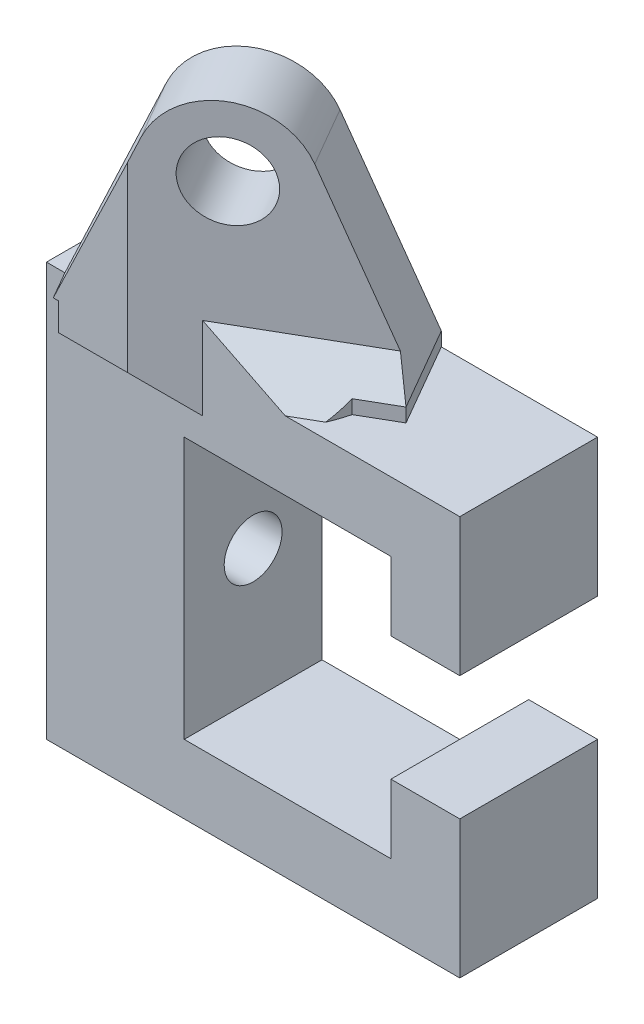
SolidWorks part; units mm, degrees
ref_plane "Front Plane" through (0, 0, 0) normal (0, 0, 1) x (1, 0, 0)
ref_plane "Top Plane" through (0, 0, 0) normal (0, 1, 0) x (1, 0, 0)
ref_plane "Right Plane" through (0, 0, 0) normal (1, 0, 0) x (0, 0, -1)
sketch "Sketch1" plane through (0, 0, 0) normal (0, 0, 1) x (1, 0, 0)
  line L0 (0, 0) -> (0, -23031.2068) construction
  line L1 (0, 0) -> (23031.2068, 0) construction
  line L2 (15, 5) -> (15, 0)
  line L3 (15, 0) -> (0, 0)
  line L4 (0, 0) -> (0, 19)
  line L5 (0, 19) -> (15, 19)
  line L6 (15, 19) -> (15, 14)
  line L7 (15, 14) -> (20, 14)
  line L8 (20, 14) -> (20, 24)
  line L9 (20, 24) -> (-10, 24)
  line L10 (-10, 24) -> (-10, -5)
  line L11 (-10, -5) -> (20, -5)
  line L12 (20, -5) -> (20, 5)
  line L13 (20, 5) -> (15, 5)
  dimension "D1" = 19
  dimension "D2" = 15
  dimension "D3" = 15
  dimension "D4" = 5
  dimension "D5" = 5
  dimension "D6" = 5
  dimension "D7" = 5
  dimension "D8" = 5
  dimension "D9" = 10
extrude "Boss-Extrude1" add sketch "Sketch1" along normal mid plane 10
sketch "Sketch2" plane through (-10, 0, 0) normal (-1, 0, 0) x (0, 0, 1)
  line L0 (0, 24) -> (0, -49976) construction
  line L1 (5, 24) -> (-5, 24) construction
  line L2 (-5, 9.5) -> (49995, 9.5) construction
  line L3 (-5, 24) -> (-5, -5) construction
  circle A0 centre (0, 9.5) radius 2.1
  point P4 (0, 24)
  point P9 (-5, 9.5)
  dimension "D1" = 4.2
extrude "Cut-Extrude1" cut sketch "Sketch2" against normal blind 10
sketch "Sketch3" plane through (0, 24, 0) normal (0, 1, 0) x (1, 0, 0)
  line L0 (0, -5) -> (0, 5) construction
  line L1 (0, -5) -> (0, 5) construction
  circle A0 centre (0, 0) radius 10
  dimension "D1" = 20
extrude "Boss-Extrude2" add sketch "Sketch3" along normal blind 1
ref_axis "Axis1" through (0, 30.7, 0) along (0, -1, 0)
ref_plane "Plane1" through (0, 0, 0) normal (0.5, 0, 0.866) x (0, -1, 0)
sketch "Sketch4" plane through (0, 0, 0) normal (0.5, 0, 0.866) x (0.866, 0, -0.5)
  line L0 (10, 25) -> (-10, 25) construction
  line L1 (10, 25) -> (-10, 25)
  line L2 (0, 29) -> (0, 50029) construction
  line L3 (-10, 25) -> (-4.6154, 37.9231)
  line L4 (10, 25) -> (4.6154, 37.9231)
  circle A0 centre (0, 36) radius 2.75
  circle A1 centre (0, 36) radius 10 construction
  arc A3 (4.6154, 37.9231) -> (-4.6154, 37.9231) centre (0, 36) ccw
  point P4 (0, 25)
  dimension "D1" = 5.5
  dimension "D2" = 20
  dimension "D3" = 11
  dimension "D4" = 10
extrude "Boss-Extrude3" add sketch "Sketch4" along normal blind 5
sketch "Sketch5" plane through (0, -5, 0) normal (0, -1, 0) x (1, 0, 0)
  line L0 (-20, -15) -> (30, -15)
  line L1 (30, -15) -> (30, 15)
  line L2 (30, 15) -> (-20, 15)
  line L3 (-20, 15) -> (-20, -15)
  line L4 (-10, -5) -> (20, -5)
  line L5 (20, -5) -> (20, 5)
  line L6 (20, 5) -> (-10, 5)
  line L7 (-10, 5) -> (-10, -5)
  line L8 (-10, -5) -> (20, -5)
  line L9 (20, -5) -> (20, 5)
  line L10 (20, 5) -> (-10, 5)
  line L11 (-10, 5) -> (-10, -5)
  line L12 (-12, -7) -> (22, -7)
  line L13 (22, -7) -> (22, 7)
  line L14 (22, 7) -> (-12, 7)
  line L15 (-12, 7) -> (-12, -7)
  dimension "D1" = 0
  dimension "D2" = 10
  dimension "D3" = 2
extrude "Cut-Extrude2" cut sketch "Sketch5" against normal through all contours L2 L3 L0 L1 L15 L14 L13 L12 region at (-19.4169, -5, 0)
sketch "Sketch6" plane through (0, 25, 0) normal (0, 1, 0) x (1, 0, 0)
  line L3 (7.1414, 7) -> (-7.1414, 7)
  line L4 (-8.6603, -5) -> (8.6603, 5)
  line L6 (7.1414, 7) -> (-7.1414, 7)
  line L7 (-8.6603, -5) -> (8.6603, 5)
  arc A1 (8.6603, 5) -> (7.1414, 7) centre (0, 0) ccw
  arc A4 (-7.1414, 7) -> (-8.6603, -5) centre (0, 0) ccw
  arc A5 (-7.1414, 7) -> (-8.6603, -5) centre (0, 0) ccw
  arc A6 (8.6603, 5) -> (7.1414, 7) centre (0, 0) ccw
  dimension "D1" = 0
extrude "Cut-Extrude3" cut sketch "Sketch6" against normal blind 1
sketch "Sketch7" plane through (0, 25, 0) normal (0, 1, 0) x (1, 0, 0)
  line L2 (-2.1244, -7) -> (7.1414, -7)
  line L3 (10, 0) -> (-2.1244, -7)
  line L4 (-2.1244, -7) -> (7.1414, -7)
  line L5 (10, 0) -> (-2.1244, -7)
  arc A1 (7.1414, -7) -> (10, 0) centre (0, 0) ccw
  arc A2 (7.1414, -7) -> (10, 0) centre (0, 0) ccw
  dimension "D1" = 0
extrude "Cut-Extrude4" cut sketch "Sketch7" against normal blind 1
chamfer "Chamfer1" distance 3 angle 45 1 edges at (5.6699, 24, 2.5)
chamfer "Chamfer2" distance 3 angle 45 1 edges at (-3.6603, 24, 5)
sketch "Sketch8" plane through (0, -5, 0) normal (0, -1, 0) x (1, 0, 0)
  line L0 (-10, 5) -> (-10, -5) construction
  line L1 (-10, -13.16) -> (-20.9807, -13.16)
  line L2 (-10, -13.16) -> (-10, 5.7861)
  line L3 (-10, 5.7861) -> (-20.9807, 5.7861)
  line L4 (-20.9807, -13.16) -> (-20.9807, 5.7861)
sketch "Sketch9" plane through (0, 24, 0) normal (0, 1, 0) x (1, 0, 0)
  line L2 (8.6603, 5) -> (-10, 5)
  line L3 (-10, 5) -> (-10, -5)
  line L4 (8.6603, 5) -> (-10, 5)
  line L5 (-10, 5) -> (-10, -5)
  line L8 (-10, -5) -> (-8.6603, -5)
  line L9 (-10, -5) -> (-8.6603, -5)
  line L10 (-8.6603, -5) -> (8.6603, 5)
  line L11 (-8.6603, -5) -> (8.6603, 5)
  dimension "D1" = 0
extrude "Boss-Extrude4" add sketch "Sketch9" along normal blind 1
sketch "Sketch10" plane through (0, 25, 0) normal (0, -1, 0) x (1, 0, 0)
  line L2 (8.6603, -5) -> (12.1603, 1.0622)
  line L3 (12.1603, 1.0622) -> (9.6847, 2.4915)
  line L4 (8.6603, -5) -> (12.1603, 1.0622)
  line L5 (12.1603, 1.0622) -> (9.6847, 2.4915)
  arc A1 (8.6603, -5) -> (9.6847, 2.4915) centre (0, 0) ccw
  arc A2 (8.6603, -5) -> (9.6847, 2.4915) centre (0, 0) ccw
  dimension "D1" = 0
extrude "Boss-Extrude5" add sketch "Sketch10" along normal blind 1
